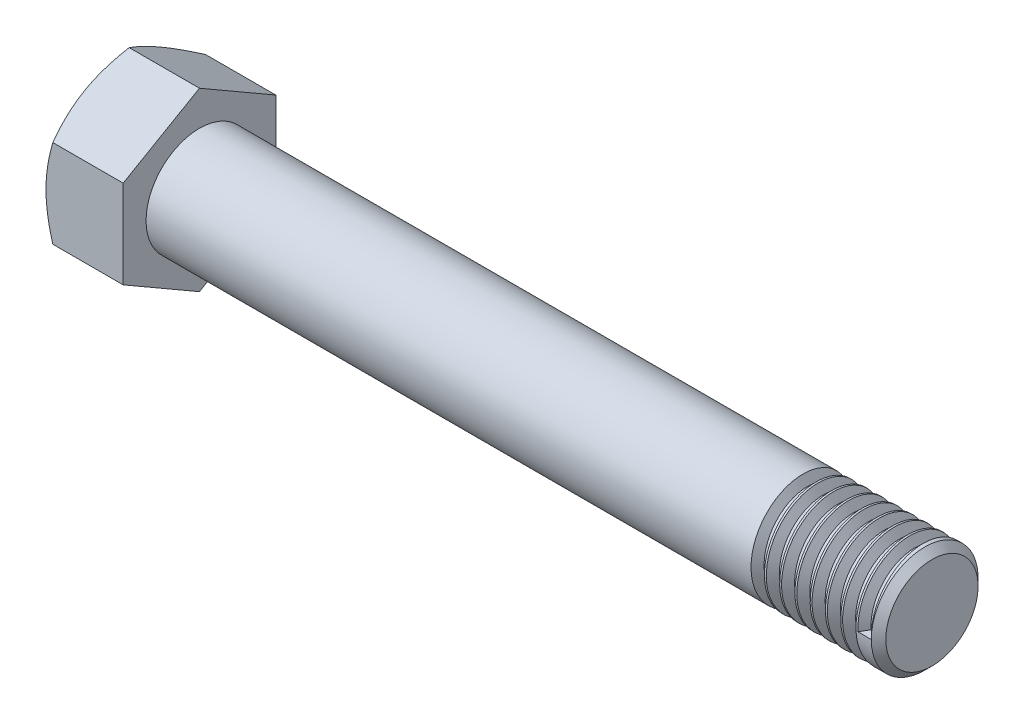
SolidWorks part; units mm, degrees
extrude "BaseHead" add sketch "Sketch1" along normal blind 8.0264
sketch "Sketch1" plane through (0, 0, 0) normal (1, 0, 0) x (0, 0, -1)
  line L0 (7.9375, 4.5827) -> (7.9375, -4.5827)
  line L1 (-7.9375, 4.5827) -> (-7.9375, -4.5827)
  line L2 (7.9375, -4.5827) -> (0, -9.1654)
  line L3 (0, -9.1654) -> (-7.9375, -4.5827)
  line L4 (7.9375, 4.5827) -> (0, 9.1654)
  line L5 (0, 9.1654) -> (-7.9375, 4.5827)
  dimension "D2" = 120
  dimension "D3" = 7.9375
  dimension "D4" = 7.9375
  dimension "D5" = 7.9375
ref_plane "Plane1" through (0, 0, 0) normal (0, 0, 1) x (1, 0, 0)
ref_plane "Plane2" through (0, 0, 0) normal (0, 1, 0) x (1, 0, 0)
ref_plane "Plane3" through (0, 0, 0) normal (1, 0, 0) x (0, 0, -1)
sketch "BodySke" plane through (0, 0, 0) normal (0, 0, 1) x (1, 0, 0)
  line L0 (0, 4.5827) -> (0, -4.5827) construction
  line L1 (0, 0) -> (84.2264, 0)
  line L2 (0, 0) -> (0, 5.5562)
  line L3 (0, 5.5562) -> (83.4708, 5.5562)
  line L4 (84.2264, 0) -> (84.2264, 4.8006)
  line L5 (8.0264, 9.1654) -> (8.0264, 4.5827) construction
  line L6 (84.2264, 4.8006) -> (83.4708, 5.5562)
  line L7 (0, 0) -> (96.52, 0) construction
  line L8 (84.2264, -4.8006) -> (83.4708, -5.5562) construction
  line L9 (0, -5.5562) -> (83.4708, -5.5562) construction
  line L10 (9.2964, 15.24) -> (9.2964, -2.54) construction
  line L11 (55.6514, 15.24) -> (55.6514, -2.54) construction
  line L12 (8.0264, 4.5827) -> (8.0264, -4.5827) construction
  dimension "Diameter" = 11.1125
revolve "BaseBody" add sketch "BodySke" angle 360 about L7
cosmetic thread "ThreadCosmetic" [suppressed] parameters "Thread_length"=28.575, "Thread_minor"=9.6012
sketch "Sketch3" plane through (0, 0, 0) normal (0, 0, 1) x (1, 0, 0)
  line L0 (0, 7.9375) -> (4.3751, 15.5154)
  line L1 (0, 9.1654) -> (0, 4.5827) construction
  line L2 (4.3751, 15.5154) -> (4.3751, 21.8654)
  line L3 (4.3751, 21.8654) -> (-12.7, 21.8654)
  line L4 (-12.7, 21.8654) -> (-12.7, 7.9375)
  line L5 (-12.7, 7.9375) -> (0, 7.9375)
  line L6 (0, 0) -> (99.06, 0) construction
  line L7 (8.0264, 9.1654) -> (0, 9.1654) construction
  dimension "D1" = 7.9375
  dimension "D2" = 6.35
  dimension "D3" = 12.7
  dimension "D4" = 6.35
  dimension "Head_ch_ang" = 30
revolve "HeadChamfer" cut sketch "Sketch3" angle 360 about L6
fillet "HeadFillet" [suppressed] radius 0.762
sketch "ThdSchSke" plane through (0, 0, 0) normal (0, 0, 1) x (1, 0, 0)
  line L0 (55.6514, -4.8006) -> (55.1223, -5.5563)
  line L1 (55.6514, -4.8006) -> (56.1805, -5.5562)
  line L2 (56.1805, -5.5562) -> (56.1805, -6.9453)
  line L3 (-3.175, 0) -> (5.1513, 0) construction
  line L5 (56.1805, -6.9453) -> (55.1223, -6.9453)
  line L6 (55.1223, -6.9453) -> (55.1223, -5.5563)
  dimension "Thread_minor" = 9.6012
  dimension "Diameter" = 11.1125
  dimension "Start" = 55.6514
revolve "ThreadSchematic" [suppressed] cut sketch "ThdSchSke" angle 360 about L3
pattern_linear "ThdSchPat" [suppressed]
thread "Thread1" pitch 1.5875 method cut profile "Thread Profile1" start angle 0, offset 0, length 11.938, pitch 1.5875, diameter 11.1125
ref_plane "Plane4" through (83.4708, 0, 5.5562) normal (0, -1, 0) x (0, 0, 1)
sketch "Thread Profile1" plane through (83.4708, 0, 5.5562) normal (0, -1, 0) x (0, 0, 1)
  line L0 (0, 0) -> (0, 1.5875) construction
  line L11 (0, 0) -> (0, 1.3891)
  line L12 (0, 1.3891) -> (-0.8593, 0.893)
  line L13 (-0.8593, 0.893) -> (-0.8593, 0.4961)
  line L15 (-0.8593, 0.4961) -> (0, 0)
  line L17 (-0.8593, 0.6945) -> (0, 0.6945) construction
  point P2 (0, 0)
  dimension "Pitch" = 1.5875
  dimension "Profile_Angle" = 60
  dimension "Profile_Land" = 0.3969
  dimension "Profile_Height" = 0.8593
equation "\"D3@Sketch1\" = \"Width_flats@Sketch1\" / 2"
equation "\"D4@Sketch1\" = \"D3@Sketch1\""
equation "\"D5@Sketch1\" = \"D4@Sketch1\""
equation "\"Thread_minor@ThreadCosmetic\" = \"Minor_dia@BodySke\""
equation "\"D1@Sketch3\" = \"Width_flats@Sketch1\" / 2"
equation "\"Thread_length@ThreadCosmetic\" = ((sgn( (\"Length@BodySke\" - \"Advance@BodySke\" ) - \"Thread_nom@BodySke\" )-1)*( (\"Length@BodySke\" - \"Advance@BodySke\" ) - \"Thread_nom@BodySke\" ))/-2+ \"Thread_nom@BodySke\""
equation "\"Thread_minor@ThdSchSke\" = \"Minor_dia@BodySke\""
equation "\"Diameter@ThdSchSke\" = \"Diameter@BodySke\""
equation "\"Overcut@ThdSchSke\" = \"Diameter@BodySke\" * 1.25"
equation "\"Start@ThdSchSke\" = \"Head_ht@BaseHead\" + \"Length@BodySke\" - \"Thread_length@ThreadCosmetic\"  '---Non-countersunk---"
equation "\"Num_threads@ThdSchPat\" = int( \"Thread_length@ThreadCosmetic\" / \"Advance@BodySke\" + 0.999 )  + 1"
equation "\"Advance@ThdSchPat\" = \"Thread_length@ThreadCosmetic\" /  (\"Num_threads@ThdSchPat\" - 1) 'relax it"
equation "\"Num_threads@ThdSchPat\" = \"Num_threads@ThdSchPat\" - sgn( \"Num_threads@ThdSchPat\" - 1) '---chamfered tips only---"
